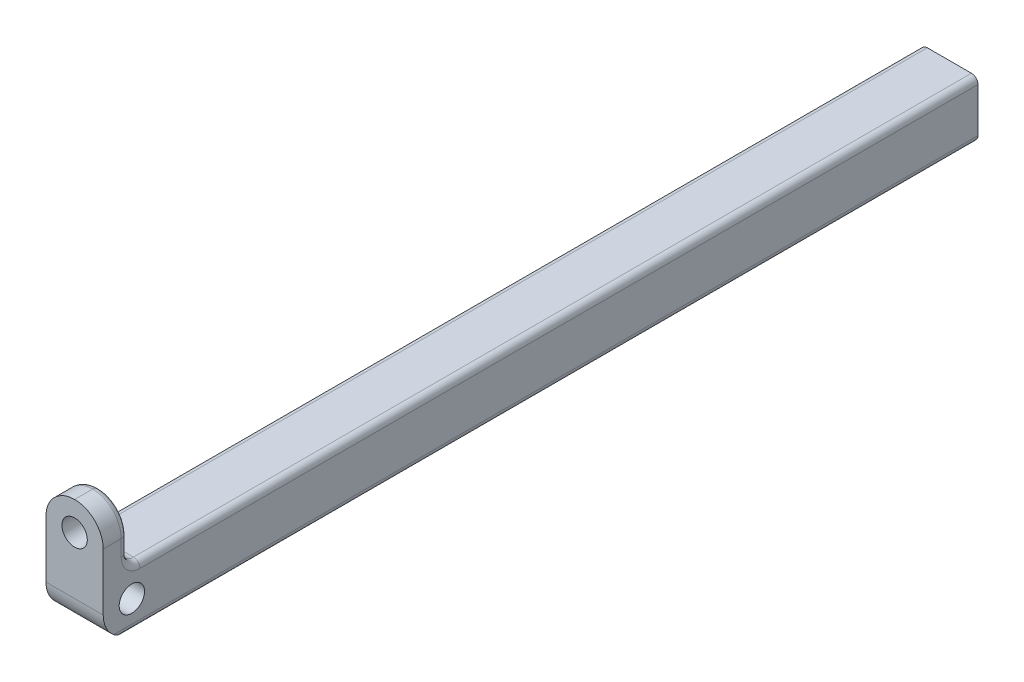
SolidWorks part; units mm, degrees
ref_plane "前视基准面" through (0, 0, 0) normal (0, 0, 1) x (1, 0, 0)
ref_plane "上视基准面" through (0, 0, 0) normal (0, 1, 0) x (1, 0, 0)
ref_plane "右视基准面" through (0, 0, 0) normal (1, 0, 0) x (0, 0, -1)
sketch "草图1" plane through (0, 0, 0) normal (0, 0, 1) x (1, 0, 0)
  line L1 (-3.5, 3.5) -> (3.5, 3.5)
  line L2 (-3.5, 3.5) -> (-3.5, -3.5)
  line L3 (-3.5, -3.5) -> (3.5, -3.5)
  line L4 (3.5, 3.5) -> (3.5, -3.5)
  line L5 (-3.5, 3.5) -> (3.5, -3.5) construction
  line L6 (-3.5, -3.5) -> (3.5, 3.5) construction
  point P0 (0, 0)
  dimension "D1" = 7
  dimension "D2" = 7
extrude "凸台-拉伸1" add sketch "草图1" along normal blind 107
fillet "圆角1" radius 3.5 1 edges at (0, -3.5, 107)
sketch "草图5" plane through (3.5, 0, 0) normal (1, 0, 0) x (0, 0, -1)
  circle A0 centre (-103.5, 0) radius 1.55
  dimension "D1" = 3.1
extrude "切除-拉伸2" cut sketch "草图5" against normal through all
sketch "草图6" plane through (0, 3.5, 0) normal (0, 1, 0) x (1, 0, 0)
  line L0 (-3.5, -107) -> (-3.5, -104)
  line L1 (-3.5, -107) -> (-3.5, 0) construction
  line L2 (-3.5, -104) -> (3.5, -104)
  line L3 (3.5, -107) -> (3.5, 0) construction
  line L4 (3.5, -104) -> (3.5, -107)
  line L5 (3.5, -107) -> (-3.5, -107)
  dimension "D1" = 3
extrude "凸台-拉伸2" add sketch "草图6" along normal blind 7
fillet "圆角2" radius 3.5 2 edges at (3.5, 10.5, 105.5) (-3.5, 10.5, 105.5)
sketch "草图7" plane through (0, 0, 104) normal (0, 0, -1) x (-1, 0, 0)
  circle A0 centre (0, 7) radius 1.55
  dimension "D1" = 3.1
extrude "切除-拉伸4" cut sketch "草图7" against normal through all
fillet "圆角3" radius 1.5 1 edges
fillet "圆角4" radius 0.8 8 edges at (-3.5, 3.9393, 103.5607) (-2.4749, 9.4749, 104) (2.4749, 9.4749, 104) (3.5, 3.9393, 103.5607)
fillet "圆角5" radius 0.8 2 edges at (-3.5, -3.5, 51.75) (3.5, -3.5, 51.75) tangent propagation no
